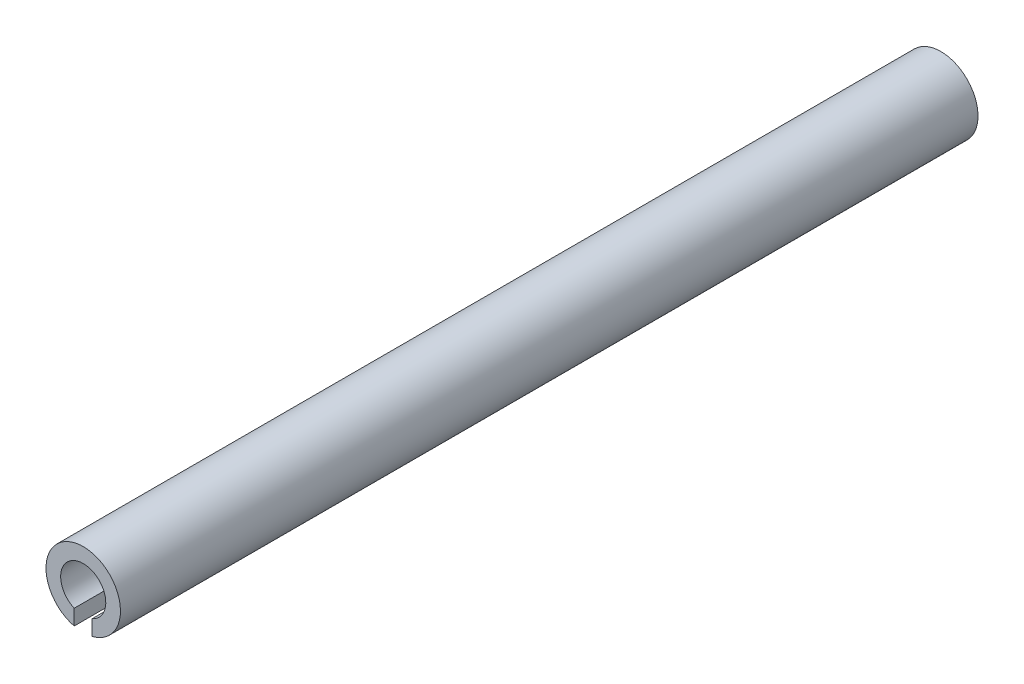
SolidWorks part; units mm, degrees
ref_plane "Front Plane" through (0, 0, 0) normal (0, 0, 1) x (1, 0, 0)
ref_plane "Top Plane" through (0, 0, 0) normal (0, 1, 0) x (1, 0, 0)
ref_plane "Right Plane" through (0, 0, 0) normal (1, 0, 0) x (0, 0, -1)
sketch "Sketch1" plane through (0, 0, 0) normal (0, 0, 1) x (1, 0, 0)
  line L1 (-0.4, 0) -> (0.4, 0)
  line L2 (-0.4, 0) -> (-0.4, -2.2024)
  line L3 (-0.4, -2.2024) -> (0.4, -2.2024)
  line L4 (0.4, 0) -> (0.4, -2.2024)
  circle A0 centre (0, 0) radius 1.65
  circle A1 centre (0, 0) radius 1
  dimension "D1" = 3.3
  dimension "D2" = 2
  dimension "D4" = 0.4
  dimension "D3" = 0.8
  dimension "D5" = 2.2024
extrude "Boss-Extrude1" add sketch "Sketch1" along normal blind 38 contours A1 L4 A0 L2 region at (-0.4463, -1.2586, 0)
